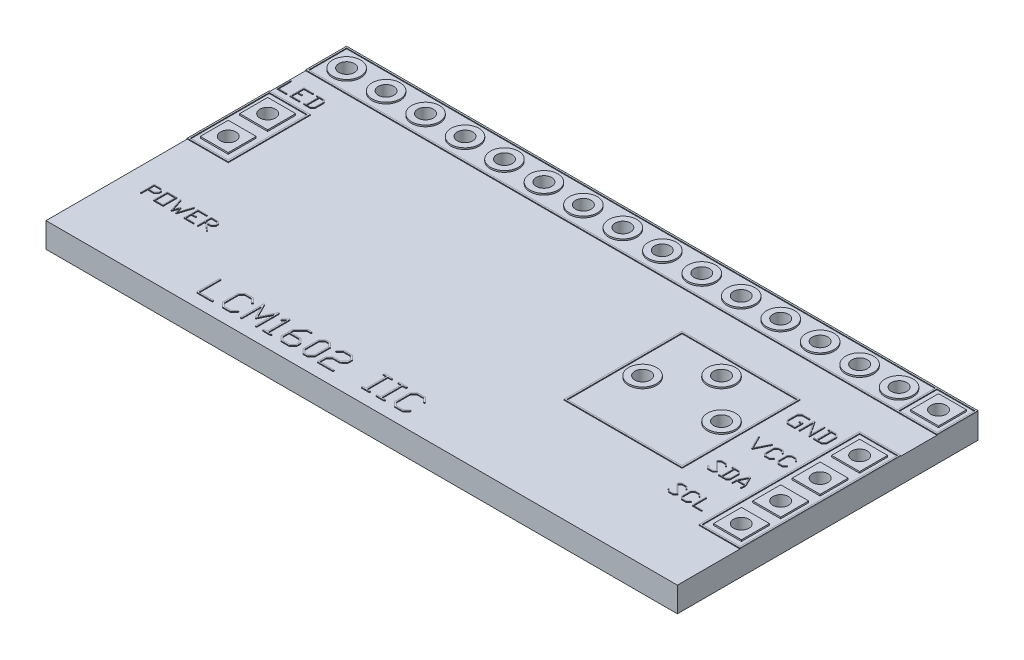
SolidWorks part; units mm, degrees
material "E-Glass Fiber"
ref_plane "Front Plane" through (0, 0, 0) normal (0, 0, 1) x (1, 0, 0)
ref_plane "Top Plane" through (0, 0, 0) normal (0, 1, 0) x (1, 0, 0)
ref_plane "Right Plane" through (0, 0, 0) normal (1, 0, 0) x (0, 0, -1)
sketch "Sketch2" plane through (0, 0, 0) normal (0, 1, 0) x (1, 0, 0)
  line L0 (-1.27, 1.27) -> (1.27, -1.27) construction
  line L1 (-1.27, 1.27) -> (1.27, 1.27)
  line L2 (-1.27, 1.27) -> (-1.27, -1.27)
  line L3 (-1.27, -1.27) -> (1.27, -1.27)
  line L4 (1.27, 1.27) -> (1.27, -1.27)
  line L5 (1.27, 1.27) -> (3.81, 1.27)
  line L6 (1.27, 1.27) -> (1.27, -1.27)
  line L7 (3.81, 1.27) -> (3.81, -1.27)
  line L8 (1.27, -1.27) -> (3.81, -1.27)
  line L9 (3.81, 1.27) -> (6.35, 1.27)
  line L10 (3.81, 1.27) -> (3.81, -1.27)
  line L11 (6.35, 1.27) -> (6.35, -1.27)
  line L12 (3.81, -1.27) -> (6.35, -1.27)
  line L13 (6.35, 1.27) -> (8.89, 1.27)
  line L14 (6.35, 1.27) -> (6.35, -1.27)
  line L15 (8.89, 1.27) -> (8.89, -1.27)
  line L16 (6.35, -1.27) -> (8.89, -1.27)
  line L17 (8.89, 1.27) -> (11.43, 1.27)
  line L18 (8.89, 1.27) -> (8.89, -1.27)
  line L19 (11.43, 1.27) -> (11.43, -1.27)
  line L20 (8.89, -1.27) -> (11.43, -1.27)
  line L21 (11.43, 1.27) -> (13.97, 1.27)
  line L22 (11.43, 1.27) -> (11.43, -1.27)
  line L23 (13.97, 1.27) -> (13.97, -1.27)
  line L24 (11.43, -1.27) -> (13.97, -1.27)
  line L25 (13.97, 1.27) -> (16.51, 1.27)
  line L26 (13.97, 1.27) -> (13.97, -1.27)
  line L27 (16.51, 1.27) -> (16.51, -1.27)
  line L28 (13.97, -1.27) -> (16.51, -1.27)
  line L29 (16.51, 1.27) -> (19.05, 1.27)
  line L30 (16.51, 1.27) -> (16.51, -1.27)
  line L31 (19.05, 1.27) -> (19.05, -1.27)
  line L32 (16.51, -1.27) -> (19.05, -1.27)
  line L33 (19.05, 1.27) -> (21.59, 1.27)
  line L34 (19.05, 1.27) -> (19.05, -1.27)
  line L35 (21.59, 1.27) -> (21.59, -1.27)
  line L36 (19.05, -1.27) -> (21.59, -1.27)
  line L37 (21.59, 1.27) -> (24.13, 1.27)
  line L38 (21.59, 1.27) -> (21.59, -1.27)
  line L39 (24.13, 1.27) -> (24.13, -1.27)
  line L40 (21.59, -1.27) -> (24.13, -1.27)
  line L41 (24.13, 1.27) -> (26.67, 1.27)
  line L42 (24.13, 1.27) -> (24.13, -1.27)
  line L43 (26.67, 1.27) -> (26.67, -1.27)
  line L44 (24.13, -1.27) -> (26.67, -1.27)
  line L45 (26.67, 1.27) -> (29.21, 1.27)
  line L46 (26.67, 1.27) -> (26.67, -1.27)
  line L47 (29.21, 1.27) -> (29.21, -1.27)
  line L48 (26.67, -1.27) -> (29.21, -1.27)
  line L49 (29.21, 1.27) -> (31.75, 1.27)
  line L50 (29.21, 1.27) -> (29.21, -1.27)
  line L51 (31.75, 1.27) -> (31.75, -1.27)
  line L52 (29.21, -1.27) -> (31.75, -1.27)
  line L53 (31.75, 1.27) -> (34.29, 1.27)
  line L54 (31.75, 1.27) -> (31.75, -1.27)
  line L55 (34.29, 1.27) -> (34.29, -1.27)
  line L56 (31.75, -1.27) -> (34.29, -1.27)
  line L57 (34.29, 1.27) -> (36.83, 1.27)
  line L58 (34.29, 1.27) -> (34.29, -1.27)
  line L59 (36.83, 1.27) -> (36.83, -1.27)
  line L60 (34.29, -1.27) -> (36.83, -1.27)
  line L61 (36.83, 1.27) -> (39.37, 1.27)
  line L62 (36.83, 1.27) -> (36.83, -1.27)
  line L63 (39.37, 1.27) -> (39.37, -1.27)
  line L64 (36.83, -1.27) -> (39.37, -1.27)
  line L65 (1.27, -1.27) -> (3.81, -1.27)
  line L66 (1.27, -1.27) -> (1.27, -3.81)
  line L67 (3.81, -1.27) -> (3.81, -3.81)
  line L68 (1.27, -3.81) -> (3.81, -3.81)
  line L69 (3.81, -1.27) -> (6.35, -1.27)
  line L70 (3.81, -1.27) -> (3.81, -3.81)
  line L71 (6.35, -1.27) -> (6.35, -3.81)
  line L72 (3.81, -3.81) -> (6.35, -3.81)
  line L73 (6.35, -1.27) -> (8.89, -1.27)
  line L74 (6.35, -1.27) -> (6.35, -3.81)
  line L75 (8.89, -1.27) -> (8.89, -3.81)
  line L76 (6.35, -3.81) -> (8.89, -3.81)
  line L77 (8.89, -1.27) -> (11.43, -1.27)
  line L78 (8.89, -1.27) -> (8.89, -3.81)
  line L79 (11.43, -1.27) -> (11.43, -3.81)
  line L80 (8.89, -3.81) -> (11.43, -3.81)
  line L81 (11.43, -1.27) -> (13.97, -1.27)
  line L82 (11.43, -1.27) -> (11.43, -3.81)
  line L83 (13.97, -1.27) -> (13.97, -3.81)
  line L84 (11.43, -3.81) -> (13.97, -3.81)
  line L85 (13.97, -1.27) -> (16.51, -1.27)
  line L86 (13.97, -1.27) -> (13.97, -3.81)
  line L87 (16.51, -1.27) -> (16.51, -3.81)
  line L88 (13.97, -3.81) -> (16.51, -3.81)
  line L89 (16.51, -1.27) -> (19.05, -1.27)
  line L90 (16.51, -1.27) -> (16.51, -3.81)
  line L91 (19.05, -1.27) -> (19.05, -3.81)
  line L92 (16.51, -3.81) -> (19.05, -3.81)
  line L93 (19.05, -1.27) -> (21.59, -1.27)
  line L94 (19.05, -1.27) -> (19.05, -3.81)
  line L95 (21.59, -1.27) -> (21.59, -3.81)
  line L96 (19.05, -3.81) -> (21.59, -3.81)
  line L97 (21.59, -1.27) -> (24.13, -1.27)
  line L98 (21.59, -1.27) -> (21.59, -3.81)
  line L99 (24.13, -1.27) -> (24.13, -3.81)
  line L100 (21.59, -3.81) -> (24.13, -3.81)
  line L101 (24.13, -1.27) -> (26.67, -1.27)
  line L102 (24.13, -1.27) -> (24.13, -3.81)
  line L103 (26.67, -1.27) -> (26.67, -3.81)
  line L104 (24.13, -3.81) -> (26.67, -3.81)
  line L105 (26.67, -1.27) -> (29.21, -1.27)
  line L106 (26.67, -1.27) -> (26.67, -3.81)
  line L107 (29.21, -1.27) -> (29.21, -3.81)
  line L108 (26.67, -3.81) -> (29.21, -3.81)
  line L109 (29.21, -1.27) -> (31.75, -1.27)
  line L110 (29.21, -1.27) -> (29.21, -3.81)
  line L111 (31.75, -1.27) -> (31.75, -3.81)
  line L112 (29.21, -3.81) -> (31.75, -3.81)
  line L113 (31.75, -1.27) -> (34.29, -1.27)
  line L114 (31.75, -1.27) -> (31.75, -3.81)
  line L115 (34.29, -1.27) -> (34.29, -3.81)
  line L116 (31.75, -3.81) -> (34.29, -3.81)
  line L117 (34.29, -1.27) -> (36.83, -1.27)
  line L118 (34.29, -1.27) -> (34.29, -3.81)
  line L119 (36.83, -1.27) -> (36.83, -3.81)
  line L120 (34.29, -3.81) -> (36.83, -3.81)
  line L121 (36.83, -1.27) -> (39.37, -1.27)
  line L122 (36.83, -1.27) -> (36.83, -3.81)
  line L123 (39.37, -1.27) -> (39.37, -3.81)
  line L124 (36.83, -3.81) -> (39.37, -3.81)
  line L125 (1.27, -3.81) -> (3.81, -3.81)
  line L126 (1.27, -3.81) -> (1.27, -6.35)
  line L127 (3.81, -3.81) -> (3.81, -6.35)
  line L128 (1.27, -6.35) -> (3.81, -6.35)
  line L129 (3.81, -3.81) -> (6.35, -3.81)
  line L130 (3.81, -3.81) -> (3.81, -6.35)
  line L131 (6.35, -3.81) -> (6.35, -6.35)
  line L132 (3.81, -6.35) -> (6.35, -6.35)
  line L133 (6.35, -3.81) -> (8.89, -3.81)
  line L134 (6.35, -3.81) -> (6.35, -6.35)
  line L135 (8.89, -3.81) -> (8.89, -6.35)
  line L136 (6.35, -6.35) -> (8.89, -6.35)
  line L137 (8.89, -3.81) -> (11.43, -3.81)
  line L138 (8.89, -3.81) -> (8.89, -6.35)
  line L139 (11.43, -3.81) -> (11.43, -6.35)
  line L140 (8.89, -6.35) -> (11.43, -6.35)
  line L141 (11.43, -3.81) -> (13.97, -3.81)
  line L142 (11.43, -3.81) -> (11.43, -6.35)
  line L143 (13.97, -3.81) -> (13.97, -6.35)
  line L144 (11.43, -6.35) -> (13.97, -6.35)
  line L145 (13.97, -3.81) -> (16.51, -3.81)
  line L146 (13.97, -3.81) -> (13.97, -6.35)
  line L147 (16.51, -3.81) -> (16.51, -6.35)
  line L148 (13.97, -6.35) -> (16.51, -6.35)
  line L149 (16.51, -3.81) -> (19.05, -3.81)
  line L150 (16.51, -3.81) -> (16.51, -6.35)
  line L151 (19.05, -3.81) -> (19.05, -6.35)
  line L152 (16.51, -6.35) -> (19.05, -6.35)
  line L153 (19.05, -3.81) -> (21.59, -3.81)
  line L154 (19.05, -3.81) -> (19.05, -6.35)
  line L155 (21.59, -3.81) -> (21.59, -6.35)
  line L156 (19.05, -6.35) -> (21.59, -6.35)
  line L157 (21.59, -3.81) -> (24.13, -3.81)
  line L158 (21.59, -3.81) -> (21.59, -6.35)
  line L159 (24.13, -3.81) -> (24.13, -6.35)
  line L160 (21.59, -6.35) -> (24.13, -6.35)
  line L161 (24.13, -3.81) -> (26.67, -3.81)
  line L162 (24.13, -3.81) -> (24.13, -6.35)
  line L163 (26.67, -3.81) -> (26.67, -6.35)
  line L164 (24.13, -6.35) -> (26.67, -6.35)
  line L165 (26.67, -3.81) -> (29.21, -3.81)
  line L166 (26.67, -3.81) -> (26.67, -6.35)
  line L167 (29.21, -3.81) -> (29.21, -6.35)
  line L168 (26.67, -6.35) -> (29.21, -6.35)
  line L169 (29.21, -3.81) -> (31.75, -3.81)
  line L170 (29.21, -3.81) -> (29.21, -6.35)
  line L171 (31.75, -3.81) -> (31.75, -6.35)
  line L172 (29.21, -6.35) -> (31.75, -6.35)
  line L173 (31.75, -3.81) -> (34.29, -3.81)
  line L174 (31.75, -3.81) -> (31.75, -6.35)
  line L175 (34.29, -3.81) -> (34.29, -6.35)
  line L176 (31.75, -6.35) -> (34.29, -6.35)
  line L177 (34.29, -3.81) -> (36.83, -3.81)
  line L178 (34.29, -3.81) -> (34.29, -6.35)
  line L179 (36.83, -3.81) -> (36.83, -6.35)
  line L180 (34.29, -6.35) -> (36.83, -6.35)
  line L181 (36.83, -3.81) -> (39.37, -3.81)
  line L182 (36.83, -3.81) -> (36.83, -6.35)
  line L183 (39.37, -3.81) -> (39.37, -6.35)
  line L184 (36.83, -6.35) -> (39.37, -6.35)
  line L185 (1.27, -6.35) -> (3.81, -6.35)
  line L186 (1.27, -6.35) -> (1.27, -8.89)
  line L187 (3.81, -6.35) -> (3.81, -8.89)
  line L188 (1.27, -8.89) -> (3.81, -8.89)
  line L189 (3.81, -6.35) -> (6.35, -6.35)
  line L190 (3.81, -6.35) -> (3.81, -8.89)
  line L191 (6.35, -6.35) -> (6.35, -8.89)
  line L192 (3.81, -8.89) -> (6.35, -8.89)
  line L193 (6.35, -6.35) -> (8.89, -6.35)
  line L194 (6.35, -6.35) -> (6.35, -8.89)
  line L195 (8.89, -6.35) -> (8.89, -8.89)
  line L196 (6.35, -8.89) -> (8.89, -8.89)
  line L197 (8.89, -6.35) -> (11.43, -6.35)
  line L198 (8.89, -6.35) -> (8.89, -8.89)
  line L199 (11.43, -6.35) -> (11.43, -8.89)
  line L200 (8.89, -8.89) -> (11.43, -8.89)
  line L201 (11.43, -6.35) -> (13.97, -6.35)
  line L202 (11.43, -6.35) -> (11.43, -8.89)
  line L203 (13.97, -6.35) -> (13.97, -8.89)
  line L204 (11.43, -8.89) -> (13.97, -8.89)
  line L205 (13.97, -6.35) -> (16.51, -6.35)
  line L206 (13.97, -6.35) -> (13.97, -8.89)
  line L207 (16.51, -6.35) -> (16.51, -8.89)
  line L208 (13.97, -8.89) -> (16.51, -8.89)
  line L209 (16.51, -6.35) -> (19.05, -6.35)
  line L210 (16.51, -6.35) -> (16.51, -8.89)
  line L211 (19.05, -6.35) -> (19.05, -8.89)
  line L212 (16.51, -8.89) -> (19.05, -8.89)
  line L213 (19.05, -6.35) -> (21.59, -6.35)
  line L214 (19.05, -6.35) -> (19.05, -8.89)
  line L215 (21.59, -6.35) -> (21.59, -8.89)
  line L216 (19.05, -8.89) -> (21.59, -8.89)
  line L217 (21.59, -6.35) -> (24.13, -6.35)
  line L218 (21.59, -6.35) -> (21.59, -8.89)
  line L219 (24.13, -6.35) -> (24.13, -8.89)
  line L220 (21.59, -8.89) -> (24.13, -8.89)
  line L221 (24.13, -6.35) -> (26.67, -6.35)
  line L222 (24.13, -6.35) -> (24.13, -8.89)
  line L223 (26.67, -6.35) -> (26.67, -8.89)
  line L224 (24.13, -8.89) -> (26.67, -8.89)
  line L225 (26.67, -6.35) -> (29.21, -6.35)
  line L226 (26.67, -6.35) -> (26.67, -8.89)
  line L227 (29.21, -6.35) -> (29.21, -8.89)
  line L228 (26.67, -8.89) -> (29.21, -8.89)
  line L229 (29.21, -6.35) -> (31.75, -6.35)
  line L230 (29.21, -6.35) -> (29.21, -8.89)
  line L231 (31.75, -6.35) -> (31.75, -8.89)
  line L232 (29.21, -8.89) -> (31.75, -8.89)
  line L233 (31.75, -6.35) -> (34.29, -6.35)
  line L234 (31.75, -6.35) -> (31.75, -8.89)
  line L235 (34.29, -6.35) -> (34.29, -8.89)
  line L236 (31.75, -8.89) -> (34.29, -8.89)
  line L237 (34.29, -6.35) -> (36.83, -6.35)
  line L238 (34.29, -6.35) -> (34.29, -8.89)
  line L239 (36.83, -6.35) -> (36.83, -8.89)
  line L240 (34.29, -8.89) -> (36.83, -8.89)
  line L241 (36.83, -6.35) -> (39.37, -6.35)
  line L242 (36.83, -6.35) -> (36.83, -8.89)
  line L243 (39.37, -6.35) -> (39.37, -8.89)
  line L244 (36.83, -8.89) -> (39.37, -8.89)
  line L245 (1.27, -8.89) -> (3.81, -8.89)
  line L246 (1.27, -8.89) -> (1.27, -11.43)
  line L247 (3.81, -8.89) -> (3.81, -11.43)
  line L248 (1.27, -11.43) -> (3.81, -11.43)
  line L249 (3.81, -8.89) -> (6.35, -8.89)
  line L250 (3.81, -8.89) -> (3.81, -11.43)
  line L251 (6.35, -8.89) -> (6.35, -11.43)
  line L252 (3.81, -11.43) -> (6.35, -11.43)
  line L253 (6.35, -8.89) -> (8.89, -8.89)
  line L254 (6.35, -8.89) -> (6.35, -11.43)
  line L255 (8.89, -8.89) -> (8.89, -11.43)
  line L256 (6.35, -11.43) -> (8.89, -11.43)
  line L257 (8.89, -8.89) -> (11.43, -8.89)
  line L258 (8.89, -8.89) -> (8.89, -11.43)
  line L259 (11.43, -8.89) -> (11.43, -11.43)
  line L260 (8.89, -11.43) -> (11.43, -11.43)
  line L261 (11.43, -8.89) -> (13.97, -8.89)
  line L262 (11.43, -8.89) -> (11.43, -11.43)
  line L263 (13.97, -8.89) -> (13.97, -11.43)
  line L264 (11.43, -11.43) -> (13.97, -11.43)
  line L265 (13.97, -8.89) -> (16.51, -8.89)
  line L266 (13.97, -8.89) -> (13.97, -11.43)
  line L267 (16.51, -8.89) -> (16.51, -11.43)
  line L268 (13.97, -11.43) -> (16.51, -11.43)
  line L269 (16.51, -8.89) -> (19.05, -8.89)
  line L270 (16.51, -8.89) -> (16.51, -11.43)
  line L271 (19.05, -8.89) -> (19.05, -11.43)
  line L272 (16.51, -11.43) -> (19.05, -11.43)
  line L273 (19.05, -8.89) -> (21.59, -8.89)
  line L274 (19.05, -8.89) -> (19.05, -11.43)
  line L275 (21.59, -8.89) -> (21.59, -11.43)
  line L276 (19.05, -11.43) -> (21.59, -11.43)
  line L277 (21.59, -8.89) -> (24.13, -8.89)
  line L278 (21.59, -8.89) -> (21.59, -11.43)
  line L279 (24.13, -8.89) -> (24.13, -11.43)
  line L280 (21.59, -11.43) -> (24.13, -11.43)
  line L281 (24.13, -8.89) -> (26.67, -8.89)
  line L282 (24.13, -8.89) -> (24.13, -11.43)
  line L283 (26.67, -8.89) -> (26.67, -11.43)
  line L284 (24.13, -11.43) -> (26.67, -11.43)
  line L285 (26.67, -8.89) -> (29.21, -8.89)
  line L286 (26.67, -8.89) -> (26.67, -11.43)
  line L287 (29.21, -8.89) -> (29.21, -11.43)
  line L288 (26.67, -11.43) -> (29.21, -11.43)
  line L289 (29.21, -8.89) -> (31.75, -8.89)
  line L290 (29.21, -8.89) -> (29.21, -11.43)
  line L291 (31.75, -8.89) -> (31.75, -11.43)
  line L292 (29.21, -11.43) -> (31.75, -11.43)
  line L293 (31.75, -8.89) -> (34.29, -8.89)
  line L294 (31.75, -8.89) -> (31.75, -11.43)
  line L295 (34.29, -8.89) -> (34.29, -11.43)
  line L296 (31.75, -11.43) -> (34.29, -11.43)
  line L297 (34.29, -8.89) -> (36.83, -8.89)
  line L298 (34.29, -8.89) -> (34.29, -11.43)
  line L299 (36.83, -8.89) -> (36.83, -11.43)
  line L300 (34.29, -11.43) -> (36.83, -11.43)
  line L301 (36.83, -8.89) -> (39.37, -8.89)
  line L302 (36.83, -8.89) -> (36.83, -11.43)
  line L303 (39.37, -8.89) -> (39.37, -11.43)
  line L304 (36.83, -11.43) -> (39.37, -11.43)
  line L305 (1.27, -11.43) -> (3.81, -11.43)
  line L306 (1.27, -11.43) -> (1.27, -13.97)
  line L307 (3.81, -11.43) -> (3.81, -13.97)
  line L308 (1.27, -13.97) -> (3.81, -13.97)
  line L309 (3.81, -11.43) -> (6.35, -11.43)
  line L310 (3.81, -11.43) -> (3.81, -13.97)
  line L311 (6.35, -11.43) -> (6.35, -13.97)
  line L312 (3.81, -13.97) -> (6.35, -13.97)
  line L313 (6.35, -11.43) -> (8.89, -11.43)
  line L314 (6.35, -11.43) -> (6.35, -13.97)
  line L315 (8.89, -11.43) -> (8.89, -13.97)
  line L316 (6.35, -13.97) -> (8.89, -13.97)
  line L317 (8.89, -11.43) -> (11.43, -11.43)
  line L318 (8.89, -11.43) -> (8.89, -13.97)
  line L319 (11.43, -11.43) -> (11.43, -13.97)
  line L320 (8.89, -13.97) -> (11.43, -13.97)
  line L321 (11.43, -11.43) -> (13.97, -11.43)
  line L322 (11.43, -11.43) -> (11.43, -13.97)
  line L323 (13.97, -11.43) -> (13.97, -13.97)
  line L324 (11.43, -13.97) -> (13.97, -13.97)
  line L325 (13.97, -11.43) -> (16.51, -11.43)
  line L326 (13.97, -11.43) -> (13.97, -13.97)
  line L327 (16.51, -11.43) -> (16.51, -13.97)
  line L328 (13.97, -13.97) -> (16.51, -13.97)
  line L329 (16.51, -11.43) -> (19.05, -11.43)
  line L330 (16.51, -11.43) -> (16.51, -13.97)
  line L331 (19.05, -11.43) -> (19.05, -13.97)
  line L332 (16.51, -13.97) -> (19.05, -13.97)
  line L333 (19.05, -11.43) -> (21.59, -11.43)
  line L334 (19.05, -11.43) -> (19.05, -13.97)
  line L335 (21.59, -11.43) -> (21.59, -13.97)
  line L336 (19.05, -13.97) -> (21.59, -13.97)
  line L337 (21.59, -11.43) -> (24.13, -11.43)
  line L338 (21.59, -11.43) -> (21.59, -13.97)
  line L339 (24.13, -11.43) -> (24.13, -13.97)
  line L340 (21.59, -13.97) -> (24.13, -13.97)
  line L341 (24.13, -11.43) -> (26.67, -11.43)
  line L342 (24.13, -11.43) -> (24.13, -13.97)
  line L343 (26.67, -11.43) -> (26.67, -13.97)
  line L344 (24.13, -13.97) -> (26.67, -13.97)
  line L345 (26.67, -11.43) -> (29.21, -11.43)
  line L346 (26.67, -11.43) -> (26.67, -13.97)
  line L347 (29.21, -11.43) -> (29.21, -13.97)
  line L348 (26.67, -13.97) -> (29.21, -13.97)
  line L349 (29.21, -11.43) -> (31.75, -11.43)
  line L350 (29.21, -11.43) -> (29.21, -13.97)
  line L351 (31.75, -11.43) -> (31.75, -13.97)
  line L352 (29.21, -13.97) -> (31.75, -13.97)
  line L353 (31.75, -11.43) -> (34.29, -11.43)
  line L354 (31.75, -11.43) -> (31.75, -13.97)
  line L355 (34.29, -11.43) -> (34.29, -13.97)
  line L356 (31.75, -13.97) -> (34.29, -13.97)
  line L357 (34.29, -11.43) -> (36.83, -11.43)
  line L358 (34.29, -11.43) -> (34.29, -13.97)
  line L359 (36.83, -11.43) -> (36.83, -13.97)
  line L360 (34.29, -13.97) -> (36.83, -13.97)
  line L361 (36.83, -11.43) -> (39.37, -11.43)
  line L362 (36.83, -11.43) -> (36.83, -13.97)
  line L363 (39.37, -11.43) -> (39.37, -13.97)
  line L364 (36.83, -13.97) -> (39.37, -13.97)
  line L365 (1.27, -13.97) -> (3.81, -13.97)
  line L366 (1.27, -13.97) -> (1.27, -16.51)
  line L367 (3.81, -13.97) -> (3.81, -16.51)
  line L368 (1.27, -16.51) -> (3.81, -16.51)
  line L369 (3.81, -13.97) -> (6.35, -13.97)
  line L370 (3.81, -13.97) -> (3.81, -16.51)
  line L371 (6.35, -13.97) -> (6.35, -16.51)
  line L372 (3.81, -16.51) -> (6.35, -16.51)
  line L373 (6.35, -13.97) -> (8.89, -13.97)
  line L374 (6.35, -13.97) -> (6.35, -16.51)
  line L375 (8.89, -13.97) -> (8.89, -16.51)
  line L376 (6.35, -16.51) -> (8.89, -16.51)
  line L377 (8.89, -13.97) -> (11.43, -13.97)
  line L378 (8.89, -13.97) -> (8.89, -16.51)
  line L379 (11.43, -13.97) -> (11.43, -16.51)
  line L380 (8.89, -16.51) -> (11.43, -16.51)
  line L381 (11.43, -13.97) -> (13.97, -13.97)
  line L382 (11.43, -13.97) -> (11.43, -16.51)
  line L383 (13.97, -13.97) -> (13.97, -16.51)
  line L384 (11.43, -16.51) -> (13.97, -16.51)
  line L385 (13.97, -13.97) -> (16.51, -13.97)
  line L386 (13.97, -13.97) -> (13.97, -16.51)
  line L387 (16.51, -13.97) -> (16.51, -16.51)
  line L388 (13.97, -16.51) -> (16.51, -16.51)
  line L389 (16.51, -13.97) -> (19.05, -13.97)
  line L390 (16.51, -13.97) -> (16.51, -16.51)
  line L391 (19.05, -13.97) -> (19.05, -16.51)
  line L392 (16.51, -16.51) -> (19.05, -16.51)
  line L393 (19.05, -13.97) -> (21.59, -13.97)
  line L394 (19.05, -13.97) -> (19.05, -16.51)
  line L395 (21.59, -13.97) -> (21.59, -16.51)
  line L396 (19.05, -16.51) -> (21.59, -16.51)
  line L397 (21.59, -13.97) -> (24.13, -13.97)
  line L398 (21.59, -13.97) -> (21.59, -16.51)
  line L399 (24.13, -13.97) -> (24.13, -16.51)
  line L400 (21.59, -16.51) -> (24.13, -16.51)
  line L401 (24.13, -13.97) -> (26.67, -13.97)
  line L402 (24.13, -13.97) -> (24.13, -16.51)
  line L403 (26.67, -13.97) -> (26.67, -16.51)
  line L404 (24.13, -16.51) -> (26.67, -16.51)
  line L405 (26.67, -13.97) -> (29.21, -13.97)
  line L406 (26.67, -13.97) -> (26.67, -16.51)
  line L407 (29.21, -13.97) -> (29.21, -16.51)
  line L408 (26.67, -16.51) -> (29.21, -16.51)
  line L409 (29.21, -13.97) -> (31.75, -13.97)
  line L410 (29.21, -13.97) -> (29.21, -16.51)
  line L411 (31.75, -13.97) -> (31.75, -16.51)
  line L412 (29.21, -16.51) -> (31.75, -16.51)
  line L413 (31.75, -13.97) -> (34.29, -13.97)
  line L414 (31.75, -13.97) -> (31.75, -16.51)
  line L415 (34.29, -13.97) -> (34.29, -16.51)
  line L416 (31.75, -16.51) -> (34.29, -16.51)
  line L417 (34.29, -13.97) -> (36.83, -13.97)
  line L418 (34.29, -13.97) -> (34.29, -16.51)
  line L419 (36.83, -13.97) -> (36.83, -16.51)
  line L420 (34.29, -16.51) -> (36.83, -16.51)
  line L421 (36.83, -13.97) -> (39.37, -13.97)
  line L422 (36.83, -13.97) -> (36.83, -16.51)
  line L423 (39.37, -13.97) -> (39.37, -16.51)
  line L424 (36.83, -16.51) -> (39.37, -16.51)
  line L425 (1.27, -16.51) -> (3.81, -16.51)
  line L426 (1.27, -16.51) -> (1.27, -19.05)
  line L427 (3.81, -16.51) -> (3.81, -19.05)
  line L428 (1.27, -19.05) -> (3.81, -19.05)
  line L429 (3.81, -16.51) -> (6.35, -16.51)
  line L430 (3.81, -16.51) -> (3.81, -19.05)
  line L431 (6.35, -16.51) -> (6.35, -19.05)
  line L432 (3.81, -19.05) -> (6.35, -19.05)
  line L433 (6.35, -16.51) -> (8.89, -16.51)
  line L434 (6.35, -16.51) -> (6.35, -19.05)
  line L435 (8.89, -16.51) -> (8.89, -19.05)
  line L436 (6.35, -19.05) -> (8.89, -19.05)
  line L437 (8.89, -16.51) -> (11.43, -16.51)
  line L438 (8.89, -16.51) -> (8.89, -19.05)
  line L439 (11.43, -16.51) -> (11.43, -19.05)
  line L440 (8.89, -19.05) -> (11.43, -19.05)
  line L441 (11.43, -16.51) -> (13.97, -16.51)
  line L442 (11.43, -16.51) -> (11.43, -19.05)
  line L443 (13.97, -16.51) -> (13.97, -19.05)
  line L444 (11.43, -19.05) -> (13.97, -19.05)
  line L445 (13.97, -16.51) -> (16.51, -16.51)
  line L446 (13.97, -16.51) -> (13.97, -19.05)
  line L447 (16.51, -16.51) -> (16.51, -19.05)
  line L448 (13.97, -19.05) -> (16.51, -19.05)
  line L449 (16.51, -16.51) -> (19.05, -16.51)
  line L450 (16.51, -16.51) -> (16.51, -19.05)
  line L451 (19.05, -16.51) -> (19.05, -19.05)
  line L452 (16.51, -19.05) -> (19.05, -19.05)
  line L453 (19.05, -16.51) -> (21.59, -16.51)
  line L454 (19.05, -16.51) -> (19.05, -19.05)
  line L455 (21.59, -16.51) -> (21.59, -19.05)
  line L456 (19.05, -19.05) -> (21.59, -19.05)
  line L457 (21.59, -16.51) -> (24.13, -16.51)
  line L458 (21.59, -16.51) -> (21.59, -19.05)
  line L459 (24.13, -16.51) -> (24.13, -19.05)
  line L460 (21.59, -19.05) -> (24.13, -19.05)
  line L461 (24.13, -16.51) -> (26.67, -16.51)
  line L462 (24.13, -16.51) -> (24.13, -19.05)
  line L463 (26.67, -16.51) -> (26.67, -19.05)
  line L464 (24.13, -19.05) -> (26.67, -19.05)
  line L465 (26.67, -16.51) -> (29.21, -16.51)
  line L466 (26.67, -16.51) -> (26.67, -19.05)
  line L467 (29.21, -16.51) -> (29.21, -19.05)
  line L468 (26.67, -19.05) -> (29.21, -19.05)
  line L469 (29.21, -16.51) -> (31.75, -16.51)
  line L470 (29.21, -16.51) -> (29.21, -19.05)
  line L471 (31.75, -16.51) -> (31.75, -19.05)
  line L472 (29.21, -19.05) -> (31.75, -19.05)
  line L473 (31.75, -16.51) -> (34.29, -16.51)
  line L474 (31.75, -16.51) -> (31.75, -19.05)
  line L475 (34.29, -16.51) -> (34.29, -19.05)
  line L476 (31.75, -19.05) -> (34.29, -19.05)
  line L477 (34.29, -16.51) -> (36.83, -16.51)
  line L478 (34.29, -16.51) -> (34.29, -19.05)
  line L479 (36.83, -16.51) -> (36.83, -19.05)
  line L480 (34.29, -19.05) -> (36.83, -19.05)
  line L481 (36.83, -16.51) -> (39.37, -16.51)
  line L482 (36.83, -16.51) -> (36.83, -19.05)
  line L483 (39.37, -16.51) -> (39.37, -19.05)
  line L484 (36.83, -19.05) -> (39.37, -19.05)
  line L485 (-1.27, -1.27) -> (1.27, -1.27)
  line L486 (-1.27, -1.27) -> (-1.27, -3.81)
  line L487 (1.27, -1.27) -> (1.27, -3.81)
  line L488 (-1.27, -3.81) -> (1.27, -3.81)
  line L489 (-1.27, -3.81) -> (1.27, -3.81)
  line L490 (-1.27, -3.81) -> (-1.27, -6.35)
  line L491 (1.27, -3.81) -> (1.27, -6.35)
  line L492 (-1.27, -6.35) -> (1.27, -6.35)
  line L493 (-1.27, -6.35) -> (1.27, -6.35)
  line L494 (-1.27, -6.35) -> (-1.27, -8.89)
  line L495 (1.27, -6.35) -> (1.27, -8.89)
  line L496 (-1.27, -8.89) -> (1.27, -8.89)
  line L497 (-1.27, -8.89) -> (1.27, -8.89)
  line L498 (-1.27, -8.89) -> (-1.27, -11.43)
  line L499 (1.27, -8.89) -> (1.27, -11.43)
  line L500 (-1.27, -11.43) -> (1.27, -11.43)
  line L501 (-1.27, -11.43) -> (1.27, -11.43)
  line L502 (-1.27, -11.43) -> (-1.27, -13.97)
  line L503 (1.27, -11.43) -> (1.27, -13.97)
  line L504 (-1.27, -13.97) -> (1.27, -13.97)
  line L505 (-1.27, -13.97) -> (1.27, -13.97)
  line L506 (-1.27, -13.97) -> (-1.27, -16.51)
  line L507 (1.27, -13.97) -> (1.27, -16.51)
  line L508 (-1.27, -16.51) -> (1.27, -16.51)
  line L509 (-1.27, -16.51) -> (1.27, -16.51)
  line L510 (-1.27, -16.51) -> (-1.27, -19.05)
  line L511 (1.27, -16.51) -> (1.27, -19.05)
  line L512 (-1.27, -19.05) -> (1.27, -19.05)
  line L513 (-1.27, 1.27) -> (1.27, 1.27) construction
  line L514 (-1.27, 1.27) -> (-1.27, -1.27) construction
  line L515 (0, -11.176) -> (0, 11.176) construction
  line L516 (-22.352, 0) -> (22.352, 0) construction
  circle A0 centre (0, 0) radius 0.5
  circle A1 centre (2.54, 0) radius 0.5
  circle A2 centre (5.08, 0) radius 0.5
  circle A3 centre (7.62, 0) radius 0.5
  circle A4 centre (10.16, 0) radius 0.5
  circle A5 centre (12.7, 0) radius 0.5
  circle A6 centre (15.24, 0) radius 0.5
  circle A7 centre (17.78, 0) radius 0.5
  circle A8 centre (20.32, 0) radius 0.5
  circle A9 centre (22.86, 0) radius 0.5
  circle A10 centre (25.4, 0) radius 0.5
  circle A11 centre (27.94, 0) radius 0.5
  circle A12 centre (30.48, 0) radius 0.5
  circle A13 centre (33.02, 0) radius 0.5
  circle A14 centre (35.56, 0) radius 0.5
  circle A15 centre (38.1, 0) radius 0.5
  circle A16 centre (2.54, -2.54) radius 0.5
  circle A17 centre (5.08, -2.54) radius 0.5
  circle A18 centre (7.62, -2.54) radius 0.5
  circle A19 centre (10.16, -2.54) radius 0.5
  circle A20 centre (12.7, -2.54) radius 0.5
  circle A21 centre (15.24, -2.54) radius 0.5
  circle A22 centre (17.78, -2.54) radius 0.5
  circle A23 centre (20.32, -2.54) radius 0.5
  circle A24 centre (22.86, -2.54) radius 0.5
  circle A25 centre (25.4, -2.54) radius 0.5
  circle A26 centre (27.94, -2.54) radius 0.5
  circle A27 centre (30.48, -2.54) radius 0.5
  circle A28 centre (33.02, -2.54) radius 0.5
  circle A29 centre (35.56, -2.54) radius 0.5
  circle A30 centre (38.1, -2.54) radius 0.5
  circle A31 centre (2.54, -5.08) radius 0.5
  circle A32 centre (5.08, -5.08) radius 0.5
  circle A33 centre (7.62, -5.08) radius 0.5
  circle A34 centre (10.16, -5.08) radius 0.5
  circle A35 centre (12.7, -5.08) radius 0.5
  circle A36 centre (15.24, -5.08) radius 0.5
  circle A37 centre (17.78, -5.08) radius 0.5
  circle A38 centre (20.32, -5.08) radius 0.5
  circle A39 centre (22.86, -5.08) radius 0.5
  circle A40 centre (25.4, -5.08) radius 0.5
  circle A41 centre (27.94, -5.08) radius 0.5
  circle A42 centre (30.48, -5.08) radius 0.5
  circle A43 centre (33.02, -5.08) radius 0.5
  circle A44 centre (35.56, -5.08) radius 0.5
  circle A45 centre (38.1, -5.08) radius 0.5
  circle A46 centre (2.54, -7.62) radius 0.5
  circle A47 centre (5.08, -7.62) radius 0.5
  circle A48 centre (7.62, -7.62) radius 0.5
  circle A49 centre (10.16, -7.62) radius 0.5
  circle A50 centre (12.7, -7.62) radius 0.5
  circle A51 centre (15.24, -7.62) radius 0.5
  circle A52 centre (17.78, -7.62) radius 0.5
  circle A53 centre (20.32, -7.62) radius 0.5
  circle A54 centre (22.86, -7.62) radius 0.5
  circle A55 centre (25.4, -7.62) radius 0.5
  circle A56 centre (27.94, -7.62) radius 0.5
  circle A57 centre (30.48, -7.62) radius 0.5
  circle A58 centre (33.02, -7.62) radius 0.5
  circle A59 centre (35.56, -7.62) radius 0.5
  circle A60 centre (38.1, -7.62) radius 0.5
  circle A61 centre (2.54, -10.16) radius 0.5
  circle A62 centre (5.08, -10.16) radius 0.5
  circle A63 centre (7.62, -10.16) radius 0.5
  circle A64 centre (10.16, -10.16) radius 0.5
  circle A65 centre (12.7, -10.16) radius 0.5
  circle A66 centre (15.24, -10.16) radius 0.5
  circle A67 centre (17.78, -10.16) radius 0.5
  circle A68 centre (20.32, -10.16) radius 0.5
  circle A69 centre (22.86, -10.16) radius 0.5
  circle A70 centre (25.4, -10.16) radius 0.5
  circle A71 centre (27.94, -10.16) radius 0.5
  circle A72 centre (30.48, -10.16) radius 0.5
  circle A73 centre (33.02, -10.16) radius 0.5
  circle A74 centre (35.56, -10.16) radius 0.5
  circle A75 centre (38.1, -10.16) radius 0.5
  circle A76 centre (2.54, -12.7) radius 0.5
  circle A77 centre (5.08, -12.7) radius 0.5
  circle A78 centre (7.62, -12.7) radius 0.5
  circle A79 centre (10.16, -12.7) radius 0.5
  circle A80 centre (12.7, -12.7) radius 0.5
  circle A81 centre (15.24, -12.7) radius 0.5
  circle A82 centre (17.78, -12.7) radius 0.5
  circle A83 centre (20.32, -12.7) radius 0.5
  circle A84 centre (22.86, -12.7) radius 0.5
  circle A85 centre (25.4, -12.7) radius 0.5
  circle A86 centre (27.94, -12.7) radius 0.5
  circle A87 centre (30.48, -12.7) radius 0.5
  circle A88 centre (33.02, -12.7) radius 0.5
  circle A89 centre (35.56, -12.7) radius 0.5
  circle A90 centre (38.1, -12.7) radius 0.5
  circle A91 centre (2.54, -15.24) radius 0.5
  circle A92 centre (5.08, -15.24) radius 0.5
  circle A93 centre (7.62, -15.24) radius 0.5
  circle A94 centre (10.16, -15.24) radius 0.5
  circle A95 centre (12.7, -15.24) radius 0.5
  circle A96 centre (15.24, -15.24) radius 0.5
  circle A97 centre (17.78, -15.24) radius 0.5
  circle A98 centre (20.32, -15.24) radius 0.5
  circle A99 centre (22.86, -15.24) radius 0.5
  circle A100 centre (25.4, -15.24) radius 0.5
  circle A101 centre (27.94, -15.24) radius 0.5
  circle A102 centre (30.48, -15.24) radius 0.5
  circle A103 centre (33.02, -15.24) radius 0.5
  circle A104 centre (35.56, -15.24) radius 0.5
  circle A105 centre (38.1, -15.24) radius 0.5
  circle A106 centre (2.54, -17.78) radius 0.5
  circle A107 centre (5.08, -17.78) radius 0.5
  circle A108 centre (7.62, -17.78) radius 0.5
  circle A109 centre (10.16, -17.78) radius 0.5
  circle A110 centre (12.7, -17.78) radius 0.5
  circle A111 centre (15.24, -17.78) radius 0.5
  circle A112 centre (17.78, -17.78) radius 0.5
  circle A113 centre (20.32, -17.78) radius 0.5
  circle A114 centre (22.86, -17.78) radius 0.5
  circle A115 centre (25.4, -17.78) radius 0.5
  circle A116 centre (27.94, -17.78) radius 0.5
  circle A117 centre (30.48, -17.78) radius 0.5
  circle A118 centre (33.02, -17.78) radius 0.5
  circle A119 centre (35.56, -17.78) radius 0.5
  circle A120 centre (38.1, -17.78) radius 0.5
  circle A121 centre (0, -2.54) radius 0.5
  circle A122 centre (0, -5.08) radius 0.5
  circle A123 centre (0, -7.62) radius 0.5
  circle A124 centre (0, -10.16) radius 0.5
  circle A125 centre (0, -12.7) radius 0.5
  circle A126 centre (0, -15.24) radius 0.5
  circle A127 centre (0, -17.78) radius 0.5
  dimension "D2" = 1
  dimension "D1" = 2.54
  dimension "D5" = 2.54
  dimension "D6" = 2.54
  dimension "D3" = 16
  dimension "D4" = 8
sketch "Sketch3" plane through (0, 0, 0) normal (0, 1, 0) x (1, 0, 0)
  line L0 (39.37, -16.51) -> (39.37, -19.05) construction
  line L1 (-1.27, 1.27) -> (39.37, 1.27)
  line L2 (-1.27, 1.27) -> (-1.27, -18.08)
  line L3 (-1.27, -18.08) -> (39.37, -18.08)
  line L4 (39.37, 1.27) -> (39.37, -18.08)
  dimension "D1" = 19.35
extrude "Boss-Extrude1" add sketch "Sketch3" along normal blind 1.6
sketch "Sketch9" plane through (0, 0, 0) normal (0, 1, 0) x (1, 0, 0)
  line L0 (0, 0) -> (2.54, 0) construction
  line L1 (-0.88, 0) -> (0.88, 0) construction
  circle A0 centre (0, 0) radius 0.5
  circle A1 centre (2.54, 0) radius 0.5
  circle A2 centre (5.08, 0) radius 0.5
  circle A3 centre (7.62, 0) radius 0.5
  circle A4 centre (10.16, 0) radius 0.5
  circle A5 centre (12.7, 0) radius 0.5
  circle A6 centre (15.24, 0) radius 0.5
  circle A7 centre (17.78, 0) radius 0.5
  circle A8 centre (20.32, 0) radius 0.5
  circle A9 centre (22.86, 0) radius 0.5
  circle A10 centre (25.4, 0) radius 0.5
  circle A11 centre (27.94, 0) radius 0.5
  circle A12 centre (30.48, 0) radius 0.5
  circle A13 centre (33.02, 0) radius 0.5
  circle A14 centre (35.56, 0) radius 0.5
  circle A15 centre (38.1, 0) radius 0.5
  dimension "D1" = 1
  dimension "D3" = 2.54
  dimension "D2" = 16
extrude "Cut-Extrude1" cut sketch "Sketch9" along normal through all
sketch "Sketch10" plane through (0, 0, 0) normal (0, 1, 0) x (1, 0, 0)
  line L0 (0, -0.88) -> (0, 0.88) construction
  line L1 (-0.88, 0) -> (0.88, 0) construction
  circle A0 centre (0, -5.08) radius 0.5
  circle A1 centre (0, -7.62) radius 0.5
  dimension "D1" = 1
  dimension "D3" = 5.08
  dimension "D2" = 2.54
extrude "Cut-Extrude2" cut sketch "Sketch10" along normal through all
sketch "Sketch12" plane through (0, 1.6, 0) normal (0, 1, 0) x (1, 0, 0)
  line L0 (0, -0.88) -> (0, 0.88) construction
  line L1 (-0.88, 0) -> (0.88, 0) construction
  circle A0 centre (38.1, -5.08) radius 0.5
  circle A1 centre (38.1, -7.62) radius 0.5
  circle A2 centre (38.1, -10.16) radius 0.5
  circle A3 centre (38.1, -12.7) radius 0.5
  dimension "D1" = 1
  dimension "D2" = 38.1
  dimension "D3" = 2.54
  dimension "D4" = 2.54
  dimension "D5" = 2.54
  dimension "D6" = 5.08
extrude "Cut-Extrude3" cut sketch "Sketch12" against normal through all
sketch "Sketch13" plane through (0, 0, 0) normal (0, 1, 0) x (1, 0, 0)
  line L0 (0, -0.88) -> (0, 0.88) construction
  line L1 (-0.88, 0) -> (0.88, 0) construction
  circle A0 centre (29.21, -5.08) radius 0.5
  circle A1 centre (26.67, -7.62) radius 0.5
  circle A2 centre (31.75, -7.62) radius 0.5
  dimension "D5" = 1
  dimension "D1" = 5.08
  dimension "D2" = 2.54
  dimension "D3" = 2.54
  dimension "D4" = 29.21
  dimension "D6" = 5.08
extrude "Cut-Extrude4" cut sketch "Sketch13" along normal through all
sketch "Sketch14" plane through (0, 1.6, 0) normal (0, 1, 0) x (1, 0, 0)
  line L0 (-0.88, 0) -> (0.88, 0) construction
  line L1 (37.2, 0.9) -> (39, 0.9)
  line L2 (37.2, 0.9) -> (37.2, -0.9)
  line L3 (37.2, -0.9) -> (39, -0.9)
  line L4 (39, 0.9) -> (39, -0.9)
  line L5 (0, -0.88) -> (0, 0.88) construction
  line L6 (-0.9, -4.18) -> (0.9, -4.18)
  line L7 (-0.9, -4.18) -> (-0.9, -5.98)
  line L8 (-0.9, -5.98) -> (0.9, -5.98)
  line L9 (0.9, -4.18) -> (0.9, -5.98)
  line L10 (37.2, -4.18) -> (39, -4.18)
  line L11 (37.2, -4.18) -> (37.2, -5.98)
  line L12 (37.2, -5.98) -> (39, -5.98)
  line L13 (39, -4.18) -> (39, -5.98)
  line L14 (-0.9, -6.72) -> (0.9, -6.72)
  line L15 (-0.9, -6.72) -> (-0.9, -8.52)
  line L16 (-0.9, -8.52) -> (0.9, -8.52)
  line L17 (0.9, -6.72) -> (0.9, -8.52)
  line L18 (37.2, -6.72) -> (39, -6.72)
  line L19 (37.2, -6.72) -> (37.2, -8.52)
  line L20 (37.2, -8.52) -> (39, -8.52)
  line L21 (39, -6.72) -> (39, -8.52)
  line L22 (37.2, -9.26) -> (39, -9.26)
  line L23 (37.2, -9.26) -> (37.2, -11.06)
  line L24 (37.2, -11.06) -> (39, -11.06)
  line L25 (39, -9.26) -> (39, -11.06)
  line L26 (37.2, -11.784) -> (39, -11.784)
  line L27 (37.2, -11.784) -> (37.2, -13.584)
  line L28 (37.2, -13.584) -> (39, -13.584)
  line L29 (39, -11.784) -> (39, -13.584)
  circle A0 centre (35.56, 0) radius 0.9
  circle A1 centre (38.1, 0) radius 0.5 construction
  circle A2 centre (33.02, 0) radius 0.9
  circle A3 centre (30.48, 0) radius 0.9
  circle A4 centre (27.94, 0) radius 0.9
  circle A5 centre (25.4, 0) radius 0.9
  circle A6 centre (22.86, 0) radius 0.9
  circle A7 centre (20.32, 0) radius 0.9
  circle A8 centre (17.78, 0) radius 0.9
  circle A9 centre (15.24, 0) radius 0.9
  circle A10 centre (12.7, 0) radius 0.9
  circle A11 centre (10.16, 0) radius 0.9
  circle A12 centre (7.62, 0) radius 0.9
  circle A13 centre (5.08, 0) radius 0.9
  circle A14 centre (2.54, 0) radius 0.9
  circle A15 centre (0, 0) radius 0.9
  circle A16 centre (29.21, -5.08) radius 0.9
  circle A17 centre (26.67, -7.62) radius 0.9
  circle A18 centre (31.75, -7.62) radius 0.9
  circle A19 centre (30.48, 0) radius 0.5 construction
  circle A20 centre (38.1, 0) radius 0.5
  circle A21 centre (35.56, 0) radius 0.5
  circle A22 centre (33.02, 0) radius 0.5
  circle A23 centre (30.48, 0) radius 0.5
  circle A24 centre (27.94, 0) radius 0.5
  circle A25 centre (25.4, 0) radius 0.5
  circle A26 centre (22.86, 0) radius 0.5
  circle A27 centre (20.32, 0) radius 0.5
  circle A28 centre (17.78, 0) radius 0.5
  circle A29 centre (15.24, 0) radius 0.5
  circle A30 centre (12.7, 0) radius 0.5
  circle A31 centre (10.16, 0) radius 0.5
  circle A32 centre (7.62, 0) radius 0.5
  circle A33 centre (5.08, 0) radius 0.5
  circle A34 centre (2.54, 0) radius 0.5
  circle A35 centre (0, 0) radius 0.5
  circle A36 centre (29.21, -5.08) radius 0.5
  circle A37 centre (31.75, -7.62) radius 0.5
  circle A38 centre (26.67, -7.62) radius 0.5
  circle A39 centre (38.1, -5.08) radius 0.5 construction
  circle A40 centre (0, -5.08) radius 0.5 construction
  circle A41 centre (0, -5.08) radius 0.5
  circle A42 centre (0, -7.62) radius 0.5
  circle A43 centre (38.1, -5.08) radius 0.5
  circle A44 centre (38.1, -7.62) radius 0.5
  circle A45 centre (38.1, -10.16) radius 0.5
  circle A46 centre (38.1, -12.7) radius 0.5
  circle A47 centre (38.1, -7.62) radius 0.5 construction
  dimension "D1" = 1.8
  dimension "D3" = 0.9
  dimension "D7" = 0.9
  dimension "D2" = 1.8
  dimension "D4" = 0.9
  dimension "D5" = 1.8
  dimension "D6" = 1.8
  dimension "D8" = 2.54
  dimension "D9" = 2.54
  dimension "D10" = 2.524
  dimension "D11" = 0.9
  dimension "D12" = 0.9
  dimension "D13" = 0.9
  dimension "D14" = 2.54
extrude "Boss-Extrude2" add sketch "Sketch14" along normal blind 0.1 and the other way blind 1.7
sketch "Sketch15" plane through (0, 1.6, 0) normal (0, 1, 0) x (1, 0, 0)
  line L0 (7.62, -17.2307) -> (22.62, -17.2307) construction
  line L1 (-0.99, 0) -> (0.99, 0) construction
  line L2 (33.75, -5.55) -> (36.3801, -5.55) construction
  line L3 (33.75, -8.09) -> (36.3801, -8.09) construction
  line L4 (33.75, -10.63) -> (36.3801, -10.63) construction
  line L5 (33.75, -13.17) -> (36.3801, -13.17) construction
  line L6 (0, -0.99) -> (0, 0.99) construction
  text T0 "LCM1602 IIC" font "SWTxt" height 1.5
  text T1 "GND" font "SWTxt" height 1
  text T2 "VCC" font "SWTxt" height 0.9
  text T3 "SDA" font "SWTxt" height 0.9
  text T4 "SCL" font "SWTxt" height 0.9
  dimension "D1" = 17.2307
  dimension "D2" = 15
  dimension "D3" = 2.54
  dimension "D4" = 2.54
  dimension "D5" = 2.6301
  dimension "D6" = 2.54
  dimension "D7" = 5.55
  dimension "D8" = 33.75
  dimension "D9" = 7.62
extrude "Boss-Extrude3" add sketch "Sketch15" along normal blind 0.05 separate body
sketch "Sketch16" plane through (0, 1.6, 0) normal (0, 1, 0) x (1, 0, 0)
  line L0 (33.01, -3.82) -> (33.01, -11.42)
  line L1 (25.51, -3.92) -> (32.91, -3.92)
  line L2 (25.51, -3.92) -> (25.51, -11.32)
  line L3 (25.51, -11.32) -> (32.91, -11.32)
  line L4 (32.91, -3.92) -> (32.91, -11.32)
  line L5 (25.41, -11.42) -> (33.01, -11.42)
  line L6 (25.41, -3.82) -> (25.41, -11.42)
  line L7 (25.41, -3.82) -> (33.01, -3.82)
  line L9 (36.83, -3.81) -> (39.27, -3.81)
  line L10 (36.83, -3.81) -> (36.83, -13.954)
  line L11 (36.83, -13.954) -> (39.27, -13.954)
  line L12 (39.27, -3.81) -> (39.27, -13.954)
  line L13 (39, -4.18) -> (37.2, -4.18) construction
  line L14 (39, -5.98) -> (39, -4.18) construction
  line L15 (37.2, -13.584) -> (39, -13.584) construction
  line L16 (37.2, -6.72) -> (37.2, -8.52) construction
  line L17 (36.73, -3.71) -> (36.73, -14.054)
  line L18 (36.73, -14.054) -> (39.37, -14.054)
  line L19 (39.37, -3.71) -> (39.37, -14.054)
  line L20 (36.73, -3.71) -> (39.37, -3.71)
  line L22 (-1.17, -3.81) -> (1.27, -3.81)
  line L23 (-1.17, -3.81) -> (-1.17, -8.89)
  line L24 (-1.17, -8.89) -> (1.27, -8.89)
  line L25 (1.27, -3.81) -> (1.27, -8.89)
  line L28 (0.9, -5.98) -> (0.9, -4.18) construction
  line L29 (0.9, -4.18) -> (-0.9, -4.18) construction
  line L30 (-0.9, -8.52) -> (0.9, -8.52) construction
  line L31 (1.37, -3.71) -> (1.37, -8.99)
  line L32 (-1.27, -8.99) -> (1.37, -8.99)
  line L33 (-1.27, -3.71) -> (-1.27, -8.99)
  line L34 (-1.27, -3.71) -> (1.37, -3.71)
  line L35 (-1.27, 1.27) -> (-1.27, -18.08) construction
  line L36 (39.37, -18.08) -> (39.37, 1.27) construction
  line L37 (37.2, -0.9) -> (39, -0.9) construction
  line L38 (-1.17, 1.17) -> (36.73, 1.17)
  line L39 (-1.17, 1.17) -> (-1.17, -1.27)
  line L40 (-1.17, -1.27) -> (36.73, -1.27)
  line L41 (39.27, 1.17) -> (39.27, -1.27)
  line L42 (-1.27, 1.27) -> (39.37, 1.27)
  line L43 (39.37, 1.27) -> (39.37, -1.37)
  line L44 (-1.27, -1.37) -> (39.37, -1.37)
  line L45 (-1.27, 1.27) -> (-1.27, -1.37)
  line L46 (36.73, 1.17) -> (36.73, -1.27)
  line L47 (36.83, -1.27) -> (36.83, 1.17)
  line L48 (36.83, -1.27) -> (39.27, -1.27)
  line L49 (-1.17, -1.27) -> (39.27, -1.27) construction
  line L50 (36.83, 1.17) -> (39.27, 1.17)
  line L51 (-1.17, 1.17) -> (39.27, 1.17) construction
  circle A0 centre (29.21, -5.08) radius 0.5 construction
  circle A1 centre (31.75, -7.62) radius 0.5 construction
  point P54 (38.1, -0.9)
  dimension "D2" = 3.7
  dimension "D3" = 3.7
  dimension "D1" = 7.4
  dimension "D5" = 0.37
  dimension "D6" = 0.27
  dimension "D7" = 0.37
  dimension "D8" = 0.37
  dimension "D10" = 0.37
  dimension "D11" = 0.37
  dimension "D12" = 0.37
  dimension "D14" = 0.37
  dimension "D4" = 0.1
  dimension "D9" = 0.1
  dimension "D13" = 0.1
  dimension "D15" = 0.1
extrude "Boss-Extrude4" add sketch "Sketch16" along normal blind 0.05 separate body
sketch "Sketch17" plane through (0, 1.6, 0) normal (0, 1, 0) x (1, 0, 0)
  line L0 (-1.27, -3.3) -> (1.3792, -3.3) construction
  line L1 (0.25, -13.5) -> (7.2636, -13.5) construction
  line L2 (-1.27, 1.27) -> (-1.27, -18.08) construction
  line L3 (-0.99, 0) -> (0.99, 0) construction
  line L4 (0, -0.99) -> (0, 0.99) construction
  text T0 "LED" font "SWTxt" height 0.9
  text T1 "POWER" font "SWTxt" height 0.9
  point P11 (1.6465, -15.1616)
  dimension "D1" = 3.3
  dimension "D2" = 13.5
  dimension "D3" = 0.25
extrude "Boss-Extrude5" add sketch "Sketch17" along normal blind 0.05 separate body
